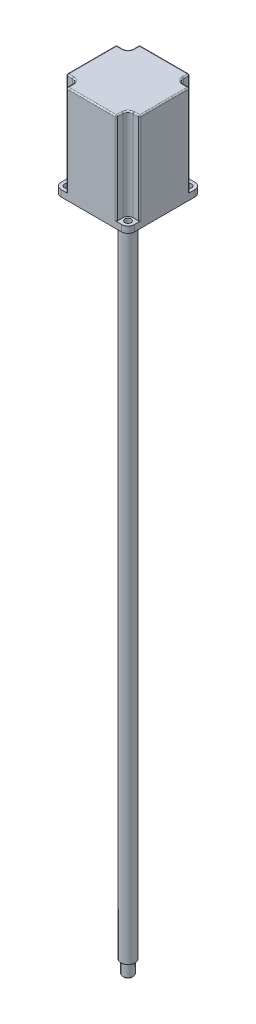
SolidWorks part; units mm, degrees
note: '?' marks a value the reader was unsure of.
material "1023 Carbon Steel Sheet (SS)"
ref_plane "Front" through (0, 0, 0) normal (0, 0, 1) x (1, 0, 0)
ref_plane "Top" through (0, 0, 0) normal (0, 1, 0) x (1, 0, 0)
ref_plane "Right" through (0, 0, 0) normal (1, 0, 0) x (0, 0, -1)
ref_axis "Axis1" through (-84.4107, 0, 0) along (1, 0, 0)?
ref_axis "Axis2" through (0, 64.3378, 0) along (0, -1, 0)?
ref_axis "Axis3" through (0, 0, -102.329) along (0, 0, 1)?
sketch "Sketch1" plane through (0, 0, 0) normal (0, 1, 0) x (1, 0, 0)
  line L1 (-28.5, -28.5) -> (28.5, -28.5)
  line L2 (-28.5, -28.5) -> (-28.5, 28.5)
  line L3 (-28.5, 28.5) -> (28.5, 28.5)
  line L4 (28.5, -28.5) -> (28.5, 28.5)
  line L5 (-28.5, -28.5) -> (28.5, 28.5) construction
  line L6 (-28.5, 28.5) -> (28.5, -28.5) construction
  point P0 (0, 0)
  dimension "D1" = 57
  dimension "D2" = 57
extrude "Extrude1" add sketch "Sketch1" along normal blind 76
hole_wizard "Ø5.0 (5) Diameter Hole1" positions "Sketch5" profile "Sketch4" hole size "Ø5.0" standard "ISO" end condition through all
sketch "Sketch5" plane through (0, 0, 0) normal (0, -1, 0) x (1, 0, 0)
  line L0 (-28.5, 28.5) -> (28.5, -28.5) construction
  line L3 (28.5, 28.5) -> (-28.5, -28.5) construction
  point P0 (-23.5, 23.5)
  point P1 (23.5, 23.5)
  point P3 (23.5, -23.5)
  point P5 (-23.5, -23.5)
  dimension "D1" = 47
  dimension "D2" = 47
sketch "Sketch4" plane through (-23.5, 0, 23.5) normal (1, 0, 0) x (0, 0, -1)
  line L0 (0, 0) -> (0, 76)
  line L1 (0, 76) -> (2.5, 76)
  line L2 (2.5, 76) -> (2.5, 0)
  line L5 (2.5, 0) -> (0, 0)
  line L11 (0, -6.35) -> (0, 107.95) construction
  dimension "Thru Hole Dia." = 5
  dimension "Thru Hole Depth" = 76
sketch "Sketch6" plane through (0, 76, 0) normal (0, 1, 0) x (1, 0, 0)
  line L0 (-19.5, 23.5) -> (-19.5, 32.5117)
  line L1 (-19.5, 32.5117) -> (-33.9089, 32.5117)
  line L2 (-33.9089, 32.5117) -> (-33.9089, 19.5)
  line L3 (-33.9089, 19.5) -> (-23.5, 19.5)
  line L4 (19.5, 23.5) -> (19.5, 36.4716)
  line L5 (19.5, 36.4716) -> (41.1684, 36.4716)
  line L6 (41.1684, 36.4716) -> (41.1684, 19.5)
  line L7 (41.1684, 19.5) -> (23.5, 19.5)
  line L8 (23.5, -19.5) -> (44.2522, -19.5)
  line L9 (44.2522, -19.5) -> (44.2522, -40.0504)
  line L10 (44.2522, -40.0504) -> (19.5, -40.0504)
  line L11 (19.5, -40.0504) -> (19.5, -23.5)
  line L12 (-23.5, -19.5) -> (-37.6708, -19.5)
  line L13 (-37.6708, -19.5) -> (-37.6708, -37.8282)
  line L14 (-37.6708, -37.8282) -> (-19.5, -37.8282)
  line L15 (-19.5, -37.8282) -> (-19.5, -23.5)
  circle A0 centre (-23.5, 23.5) radius 4
  circle A1 centre (23.5, 23.5) radius 4
  circle A2 centre (23.5, -23.5) radius 4
  circle A3 centre (-23.5, -23.5) radius 4
  circle M1 centre (-23.5, -23.5) radius 2.5
  circle M2 centre (23.5, -23.5) radius 2.5
  circle M3 centre (23.5, 23.5) radius 2.5
  circle M4 centre (-23.5, 23.5) radius 2.5
  line M5 (28.5, -28.5) -> (28.5, 28.5)
  line M6 (28.5, 28.5) -> (-28.5, 28.5)
  line M7 (-28.5, 28.5) -> (-28.5, -28.5)
  line M8 (-28.5, -28.5) -> (28.5, -28.5)
  dimension "D1" = 8
  dimension "D2" = 8
  dimension "D3" = 8
  dimension "D4" = 8
extrude "Extrude4" cut sketch "Sketch6" against normal blind 71 contours L2 L3 L0 L1 M7 M6 | A0 L0 L3 M6 M7 | A0 M4 | L7 L6 L5 L4 M6 M5 | A1 L7 L4 M5 M6 | A1 M3 | A2 M2 | A2 L11 L8 M8 M5 | L11 L10 L9 L8 M5 M8 | L14 L15 L12 L13 M8 M7 | A3 L12 L15 M7 M8 | A3 M1
fillet "Fillet1" radius 5 4 edges at (-28.5, 2.5, 28.5) (28.5, 2.5, 28.5) (28.5, 2.5, -28.5) (-28.5, 2.5, -28.5)
sketch "Sketch7" plane through (0, 76, 0) normal (0, 1, 0) x (1, 0, 0)
  circle A0 centre (0, 0) radius 3
  dimension "D1" = 6
extrude "Extrude5" add sketch "Sketch7" against normal blind 101 separate body
sketch "Sketch8" plane through (0, 0, 0) normal (0, -1, 0) x (1, 0, 0)
  circle A0 centre (0, 0) radius 19.05
  dimension "D1" = 38.1
extrude "Extrude6" add sketch "Sketch8" along normal blind 3
fillet "Fillet2" radius 1 24 edges at (-26, 76, 19.5) (-20.6716, 76, 20.6716) (-19.5, 76, 26) (0, 76, 28.5) (19.5, 76, 26) (20.6716, 76, 20.6716) (26, 76, 19.5) (28.5, 76, 0) (19.5, 76, -26) (26, 76, -19.5) (20.6716, 76, -20.6716) (-26, 76, -19.5) (-19.5, 76, -26) (-20.6716, 76, -20.6716) (0, 76, -28.5) (-28.5, 76, 0) (-19.5, 40.5, 28.5) (-28.5, 40.5, 19.5) (-28.5, 40.5, -19.5) (-19.5, 40.5, -28.5) (19.5, 40.5, -28.5) (28.5, 40.5, -19.5) (28.5, 40.5, 19.5) (19.5, 40.5, 28.5)
sketch "Sketch9" plane through (0, 0, 0) normal (0, -1, 0) x (1, 0, 0)
  circle A0 centre (0, 0) radius 5.5
  dimension "D1" = 11
extrude "Boss-Extrude1" add sketch "Sketch9" along normal blind 516
chamfer "Chamfer1" distance 0.5 angle 45 1 edges at (0, -516, -5.5)
sketch "Sketch10" plane through (0, -516, 0) normal (0, -1, 0) x (1, 0, 0)
  circle A0 centre (0, 0) radius 4
  dimension "D1" = 8
extrude "Boss-Extrude2" add sketch "Sketch10" along normal blind 10
chamfer "Chamfer2" distance 0.5 angle 45 1 edges at (0, -526, -4)
